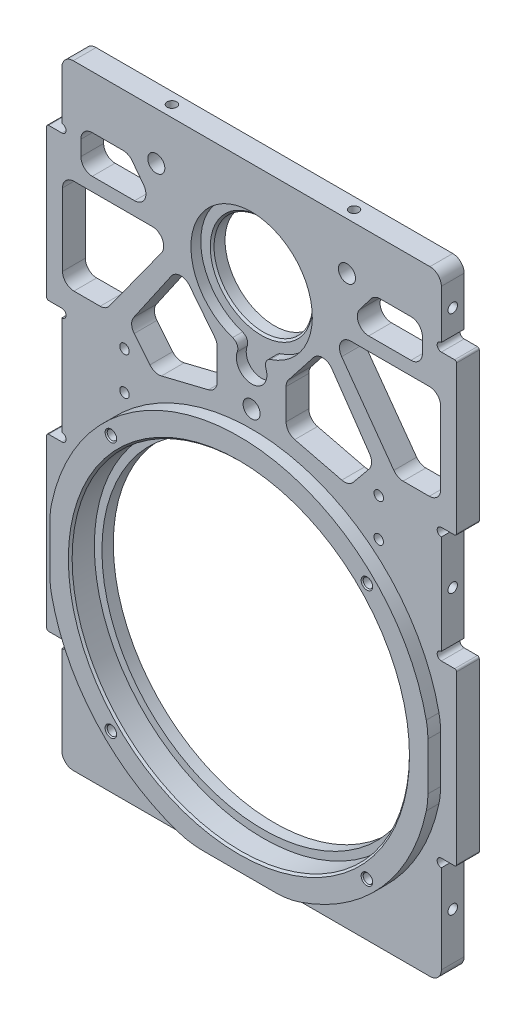
SolidWorks part; units mm, degrees
material "Thornel Mat VMA"
ref_plane "前视基准面" through (0, 0, 0) normal (0, 0, 1) x (1, 0, 0)
ref_plane "上视基准面" through (0, 0, 0) normal (0, 1, 0) x (1, 0, 0)
ref_plane "右视基准面" through (0, 0, 0) normal (1, 0, 0) x (0, 0, -1)
sketch "草图1" plane through (0, 0, 0) normal (0, 0, 1) x (1, 0, 0)
  line L1 (50, -123) -> (-50, -123)
  line L2 (50, -123) -> (50, 123)
  line L3 (50, 123) -> (-50, 123)
  line L4 (-50, -123) -> (-50, 123)
  line L5 (50, -123) -> (-50, 123) construction
  line L6 (50, 123) -> (-50, -123) construction
  circle A0 centre (0, 0) radius 44.45
  point P0 (0, 0)
  dimension "D2" = 88.9
  dimension "D3" = 123
  dimension "D1" = 100
extrude "凸台-拉伸1" add sketch "草图1" along normal blind 6
sketch "草图2" plane through (0, 0, 6) normal (0, 0, 1) x (1, 0, 0)
  line L0 (0, 0) -> (0, 84) construction
  circle A0 centre (0, 84) radius 13
  dimension "D1" = 26
  dimension "D2" = 84
extrude "切除-拉伸1" cut sketch "草图2" against normal blind 6
sketch "草图3" plane through (0, 0, 6) normal (0, 0, 1) x (1, 0, 0)
  line L0 (0, 84) -> (0, 55) construction
  circle A0 centre (0, 84) radius 29 construction
  circle A1 centre (0, 55) radius 2
  circle A2 centre (-25.1147, 98.5) radius 2
  circle A3 centre (25.1147, 98.5) radius 2
  point P11 (0, 84)
  dimension "D1" = 58
  dimension "D2" = 4
  dimension "D3" = 3
extrude "切除-拉伸2" cut sketch "草图3" against normal blind 10
sketch "草图4" plane through (0, 0, 6) normal (0, 0, 1) x (1, 0, 0)
  circle A0 centre (0, 84) radius 16
  dimension "D1" = 32
extrude "切除-拉伸3" cut sketch "草图4" against normal blind 2.6
sketch "草图5" plane through (0, 0, 6) normal (0, 0, 1) x (1, 0, 0)
  line L0 (0, 84) -> (0, 64.75) construction
  circle A0 centre (0, 64.75) radius 4.025
  dimension "D2" = 8.05
  dimension "D1" = 19.25
extrude "切除-拉伸4" cut sketch "草图5" against normal up to surface (2.6 mm away) up to face at (16, 84, 3.4)
fillet "圆角1" radius 2 2 edges at (2.1598, 68.1464, 4.7) (-2.1598, 68.1464, 4.7)
hole_wizard "打孔尺寸(%根据十字)槽沉头自攻螺钉的类型1" positions "3D草图6" profile "草图13" countersink size "ST4.2" standard "GB"
sketch3d "3D草图6"
  line L0 (25.1147, 98.5, 0) -> (25.1147, 98.5, 6) construction
  line L1 (-25.1147, 98.5, 0) -> (-25.1147, 98.5, 6) construction
  line L2 (0, 55, 0) -> (0, 55, 6) construction
  point P0 (25.1147, 98.5, 0)
  point P4 (-25.1147, 98.5, 0)
  point P8 (0, 55, 0)
sketch "草图13" plane through (25.1147, 98.5, 0) normal (1, 0, 0) x (0, 1, 0)
  line L0 (0, 0) -> (0, 9.8519)
  line L1 (0, 9.8519) -> (2.25, 8.5)
  line L2 (2.25, 8.5) -> (2.25, 2.45)
  line L3 (2.25, 2.45) -> (4.7, 0)
  line L5 (4.7, 0) -> (0, 0)
  line L6 (-2.25, 2.45) -> (-4.7, 0) construction
  line L10 (0, 9.8519) -> (-2.25, 8.5) construction
  line L11 (0, -6.35) -> (0, 107.95) construction
  dimension "孔直径" = 4.5
  dimension "孔深度" = 8.5
  dimension "近端锥形沉头孔直径" = 9.4
  dimension "近端锥形沉头孔角度" = 90
  dimension "导头角度" = 118
sketch "草图17" plane through (0, 0, 0) normal (0, 0, -1) x (-1, 0, 0)
  circle A0 centre (0, 0) radius 44.45 construction
  circle A1 centre (0, 0) radius 44.45
  circle A2 centre (0, 0) radius 42.45
  dimension "D1" = 2
extrude "凸台-拉伸3" add sketch "草图17" against normal blind 3
sketch "草图18" plane through (0, 0, 6) normal (0, 0, 1) x (1, 0, 0)
  circle A0 centre (0, 0) radius 44.45 construction
  circle A1 centre (0, 0) radius 44.45
  circle A2 centre (0, 0) radius 50.45
  dimension "D1" = 6
extrude "凸台-拉伸4" add sketch "草图18" along normal blind 3.35
sketch "草图20" plane through (0, 0, 9.35) normal (0, 0, 1) x (1, 0, 0)
  line L0 (0, 0) -> (47.7, 0) construction
  line L1 (0, 0) -> (33.729, 33.729) construction
  circle A0 centre (0, 0) radius 47.7 construction
  circle A1 centre (33.729, 33.729) radius 1.2
  circle A2 centre (33.729, -33.729) radius 1.2
  circle A3 centre (-33.729, -33.729) radius 1.2
  circle A4 centre (-33.729, 33.729) radius 1.2
  circle A5 centre (0, 0) radius 42.45 construction
  point P15 (0, 0)
  dimension "D1" = 5.25
  dimension "D3" = 2.4
  dimension "D2" = 45
  dimension "D4" = 4
extrude "切除-拉伸9" cut sketch "草图20" against normal blind 22.35
hole_wizard "M3 螺纹孔4" positions "3D草图8" profile "草图21" tap size "M3" standard "GB"
sketch3d "3D草图8"
  line L0 (33.729, 33.729, 0) -> (33.729, 33.729, 9.35) construction
  line L1 (33.729, -33.729, 0) -> (33.729, -33.729, 9.35) construction
  line L2 (-33.729, 33.729, 0) -> (-33.729, 33.729, 9.35) construction
  line L3 (-33.729, -33.729, 0) -> (-33.729, -33.729, 9.35) construction
  point P0 (33.729, 33.729, 9.35)
  point P4 (33.729, -33.729, 9.35)
  point P8 (-33.729, 33.729, 9.35)
  point P12 (-33.729, -33.729, 9.35)
sketch "草图21" plane through (33.729, 33.729, 9.35) normal (1, 0, 0) x (0, -1, 0)
  line L0 (0, 0) -> (0, 13.2511)
  line L1 (0, 13.2511) -> (1.25, 12.5)
  line L2 (1.25, 12.5) -> (1.25, 0.275)
  line L3 (1.25, 0.275) -> (1.525, 0)
  line L5 (1.525, 0) -> (0, 0)
  line L6 (-1.25, 0.275) -> (-1.525, 0) construction
  line L10 (0, 13.2511) -> (-1.25, 12.5) construction
  line L11 (0, -6.35) -> (0, 107.95) construction
  dimension "螺纹孔钻头直径" = 2.5
  dimension "螺纹孔钻头深度" = 12.5
  dimension "近端锥形沉头孔直径" = 3.05
  dimension "近端锥形沉头孔角度" = 90
  dimension "导头角度" = 118
cosmetic thread "孔螺蚊线15" parameters "D1"=9.35, "D2"=3
cosmetic thread "孔螺蚊线16" parameters "D1"=9.35, "D2"=3
cosmetic thread "孔螺蚊线17" parameters "D1"=9.35, "D2"=3
cosmetic thread "孔螺蚊线18" parameters "D1"=9.35, "D2"=3
chamfer "倒角1" distance 0.5 angle 45 1 edges at (44.45, 0, 9.35)
sketch "草图22" plane through (0, 0, 6) normal (0, 0, 1) x (1, 0, 0)
  line L0 (-50, -6.7233) -> (-50, -123) construction
  line L1 (50, -123) -> (-50, -123)
  line L2 (50, -123) -> (50, -51)
  line L3 (50, -51) -> (-50, -51)
  line L4 (-50, -123) -> (-50, -51)
  dimension "D1" = 72
sketch "草图23" plane through (0, 0, 6) normal (0, 0, 1) x (1, 0, 0)
  line L0 (-50, 123) -> (-50, 6.7233) construction
  line L1 (50, 123) -> (-50, 123)
  line L2 (50, 123) -> (50, 111)
  line L3 (50, 111) -> (-50, 111)
  line L4 (-50, 123) -> (-50, 111)
  dimension "D1" = 12
extrude "切除-拉伸11" cut sketch "草图23" against normal blind 10
sketch "草图24" plane through (0, 0, 6) normal (0, 0, 1) x (1, 0, 0)
  line L0 (-50, 0) -> (50, 0) construction
  line L1 (0, 0) -> (0, 122.891) construction
  line L2 (50, 6.7233) -> (50, -6.7233) construction
  line L3 (-54, 22.5) -> (-46, -22.5) construction
  line L4 (54, -22.5) -> (46, -22.5)
  line L5 (54, -22.5) -> (54, 22.5)
  line L6 (54, 22.5) -> (46, 22.5)
  line L7 (46, -22.5) -> (46, 22.5)
  line L8 (54, -22.5) -> (46, 22.5) construction
  line L9 (54, 22.5) -> (46, -22.5) construction
  line L10 (-54, -22.5) -> (-46, 22.5) construction
  line L11 (-50, 6.7233) -> (-50, -6.7233) construction
  line L12 (-46, -22.5) -> (-46, 22.5)
  line L13 (-54, 22.5) -> (-46, 22.5)
  line L14 (-54, -22.5) -> (-54, 22.5)
  line L15 (-54, -22.5) -> (-46, -22.5)
  line L16 (50, 6.7233) -> (50, 111) construction
  dimension "D1" = 45
  dimension "D2" = 4
extrude "凸台-拉伸5" add sketch "草图24" against normal up to surface (6 mm away) up to face at (34.979, 33.729, 0)
sketch "草图25" plane through (0, 0, 9.35) normal (0, 0, 1) x (1, 0, 0)
  line L0 (50, -22.5) -> (50, 22.5)
  line L1 (0, 0) -> (0, -64.4708) construction
  line L2 (50, -22.5) -> (54, -22.5)
  line L3 (54, -22.5) -> (54, 22.5)
  line L4 (54, 22.5) -> (50, 22.5)
  line L5 (49.8, -22.7) -> (49.8, 22.7)
  line L6 (54.2, 22.7) -> (49.8, 22.7)
  line L7 (54.2, -22.7) -> (54.2, 22.7)
  line L8 (49.8, -22.7) -> (54.2, -22.7)
  line L9 (-49.8, -22.7) -> (-54.2, -22.7)
  line L10 (-54.2, -22.7) -> (-54.2, 22.7)
  line L11 (-54.2, 22.7) -> (-49.8, 22.7)
  line L12 (-49.8, -22.7) -> (-49.8, 22.7)
  line L13 (-54, 22.5) -> (-50, 22.5)
  line L14 (-54, -22.5) -> (-54, 22.5)
  line L15 (-50, -22.5) -> (-54, -22.5)
  line L16 (-50, -22.5) -> (-50, 22.5)
  circle M11 centre (0, 0) radius 50.45
  dimension "D1" = 0.2
extrude "切除-拉伸12" cut sketch "草图25" against normal up to surface (3.35 mm away) contours L3 L4 L0 L2 M11 | L5 L8 L7 L6 L0 L4 L3 L2 M11 | L5 L0 M11 | L0 M11 | L15 L16 L13 L14 M11 | L16 L15 L14 L13 L12 L11 L10 L9 M11 | L16 L12 M11 | L16 M11 region at (52, -22.5456, 9.35) region at (52.0418, 0, 9.35) region at (49.897, 0, 9.35) region at (50.1801, 0, 9.35) region at (-49.897, 0, 9.35) region at (-49.8456, -15.3862, 9.35) region at (-50.1801, 0, 9.35) region at (-52.0418, 0, 9.35) up to face at (50.45, 0, 6)
fillet "圆角2" radius 20 4 edges at (-49.8, 8.0723, 7.675) (49.8, 8.0723, 7.675) (49.8, -8.0723, 7.675) (-49.8, -8.0723, 7.675)
sketch "草图26" plane through (0, 0, 6) normal (0, 0, 1) x (1, 0, 0)
  line L0 (50, -123) -> (50, -22.5) construction
  line L1 (50, 22.5) -> (50, 111) construction
  line L2 (-50, -22.5) -> (-50, -123) construction
  line L3 (-50, 111) -> (-50, 22.5) construction
  circle A0 centre (50, -23.6) radius 1.1
  circle A1 centre (50, 23.6) radius 1.1
  circle A2 centre (-50, -23.6) radius 1.1
  circle A3 centre (-50, 23.6) radius 1.1
  dimension "D1" = 2.2
extrude "切除-拉伸13" cut sketch "草图26" against normal blind 10
fillet "圆角3" radius 0.5 4 edges at (-54, -22.5, 3) (-54, 22.5, 3) (54, 22.5, 3) (54, -22.5, 3)
sketch "草图27" plane through (0, 0, 6) normal (0, 0, 1) x (1, 0, 0)
  line L0 (50, 24.7) -> (50, 111) construction
  line L1 (46, 53) -> (54, 53)
  line L2 (46, 53) -> (46, 93)
  line L3 (46, 93) -> (54, 93)
  line L4 (54, 53) -> (54, 93)
  line L5 (46, 53) -> (54, 93) construction
  line L6 (46, 93) -> (54, 53) construction
  line L7 (54, -22) -> (54, 22) construction
  line L8 (0, 0) -> (0, 27.5461) construction
  line L9 (-46, 93) -> (-54, 53) construction
  line L10 (-46, 53) -> (-54, 93) construction
  line L11 (-54, 53) -> (-54, 93)
  line L12 (-46, 93) -> (-54, 93)
  line L13 (-46, 53) -> (-46, 93)
  line L14 (-46, 53) -> (-54, 53)
  line L15 (-50, 111) -> (50, 111) construction
  point P0 (50, 73)
  point P16 (-50, 73)
  dimension "D1" = 18
  dimension "D2" = 40
extrude "凸台-拉伸6" add sketch "草图27" against normal up to surface (6 mm away) up to face at (0, -1.2, 0)
sketch "草图28" plane through (0, 0, 6) normal (0, 0, 1) x (1, 0, 0)
  line L0 (50, 24.7) -> (50, 53) construction
  line L1 (-50, 53) -> (-50, 24.7) construction
  line L2 (50, 93) -> (50, 111) construction
  line L3 (-50, 111) -> (-50, 93) construction
  circle A0 centre (50, 51.9) radius 1.1
  circle A1 centre (-50, 51.9) radius 1.1
  circle A2 centre (50, 94.1) radius 1.1
  circle A3 centre (-50, 94.1) radius 1.1
  dimension "D1" = 2.2
extrude "切除-拉伸14" cut sketch "草图28" against normal blind 10
fillet "圆角5" radius 0.5 4 edges at (-54, 93, 3) (-54, 53, 3) (54, 53, 3) (54, 93, 3)
extrude "切除-拉伸15" cut sketch "草图22" against normal blind 10
fillet "圆角6" radius 3 4 edges at (50, 111, 3) (-50, 111, 3) (-50, -51, 3) (50, -51, 3)
sketch "草图30" plane through (50, 0, 0) normal (1, 0, 0) x (0, 0, -1)
  line L0 (-6, 37.75) -> (0, 37.75) construction
  line L1 (-6, 24.7) -> (-6, 50.8) construction
  line L2 (0, 24.7) -> (0, 50.8) construction
  line L3 (-6, 101.6) -> (0, 101.6) construction
  line L4 (-6, 95.2) -> (-6, 108) construction
  line L5 (0, 95.2) -> (0, 108) construction
  line L6 (-6, -36.35) -> (0, -34.979) construction
  line L7 (-6, -48) -> (-6, -24.7) construction
  circle A0 centre (-3, -35.6645) radius 1.25
  circle A1 centre (-3, 37.75) radius 1.25
  circle A2 centre (-3, 101.6) radius 1.25
  dimension "D1" = 2.5
extrude "切除-拉伸17" cut sketch "草图30" against normal blind 8
cosmetic thread "孔螺蚊线20" parameters "D1"=8, "D2"=3
cosmetic thread "孔螺蚊线21" parameters "D1"=8, "D2"=3
cosmetic thread "孔螺蚊线22" parameters "D1"=8, "D2"=3
hole_wizard "M3 螺纹孔6" positions "3D草图10" profile "草图32" tap size "M3" standard "GB"
sketch3d "3D草图10"
  line L0 (42, -35.6645, 3) -> (50, -35.6645, 3) construction
  line L1 (42, 37.75, 3) -> (50, 37.75, 3) construction
  line L2 (42, 101.6, 3) -> (50, 101.6, 3) construction
  point P0 (50, -35.6645, 3)
  point P4 (50, 37.75, 3)
  point P8 (50, 101.6, 3)
sketch "草图32" plane through (50, -35.6645, 3) normal (0, 1, 0) x (0, 0, -1)
  line L0 (0, 0) -> (0, 11.2511)
  line L1 (0, 11.2511) -> (1.25, 10.5)
  line L2 (1.25, 10.5) -> (1.25, 0)
  line L5 (1.25, 0) -> (0, 0)
  line L10 (0, 11.2511) -> (-1.25, 10.5) construction
  line L11 (0, -6.35) -> (0, 107.95) construction
  dimension "螺纹孔钻头直径" = 2.5
  dimension "螺纹孔钻头深度" = 10.5
  dimension "导头角度" = 118
cosmetic thread "孔螺蚊线36" parameters "D1"=8, "D2"=3.5
cosmetic thread "孔螺蚊线37" parameters "D1"=8, "D2"=3.5
cosmetic thread "孔螺蚊线38" parameters "D1"=8, "D2"=3.5
mirror "镜向2" about plane through (0, 0, 0) normal (1, 0, 0) of "M3 螺纹孔6", "切除-拉伸17"
cosmetic thread "孔螺蚊线39" parameters "D1"=8, "D2"=3.5
cosmetic thread "孔螺蚊线40" parameters "D1"=8, "D2"=3.5
cosmetic thread "孔螺蚊线41" parameters "D1"=8, "D2"=3.5
cosmetic thread "孔螺蚊线52" parameters "D1"=8, "D2"=3.5
cosmetic thread "孔螺蚊线53" parameters "D1"=8, "D2"=3.5
cosmetic thread "孔螺蚊线54" parameters "D1"=8, "D2"=3
sketch "草图33" plane through (0, 0, 0) normal (0, 0, -1) x (-1, 0, 0)
  line L0 (0, 0) -> (0, 84) construction
  line L1 (0, 42) -> (-33.5, 42) construction
  line L2 (-33.5, 42) -> (-33.5, 52) construction
  circle A0 centre (-33.5, 42) radius 1.25
  circle A1 centre (33.5, 42) radius 1.25
  circle A2 centre (-33.5, 52) radius 1.25
  circle A3 centre (33.5, 52) radius 1.25
  dimension "D1" = 2.5
  dimension "D2" = 67
  dimension "D3" = 10
extrude "切除-拉伸18" cut sketch "草图33" against normal blind 10
cosmetic thread "孔螺蚊线26" parameters "D1"=6, "D2"=3
cosmetic thread "孔螺蚊线27" parameters "D1"=6, "D2"=3
cosmetic thread "孔螺蚊线28" parameters "D1"=6, "D2"=3
cosmetic thread "孔螺蚊线29" parameters "D1"=6, "D2"=3
hole_wizard "M3 螺纹孔7" positions "3D草图11" profile "草图34" tap size "M3" standard "GB"
sketch3d "3D草图11"
  line L0 (33.5, 42, 6) -> (33.5, 42, 0) construction
  line L1 (33.5, 52, 6) -> (33.5, 52, 0) construction
  line L2 (-33.5, 42, 6) -> (-33.5, 42, 0) construction
  line L3 (-33.5, 52, 6) -> (-33.5, 52, 0) construction
  point P0 (33.5, 42, 0)
  point P4 (33.5, 52, 0)
  point P8 (-33.5, 42, 0)
  point P12 (-33.5, 52, 0)
sketch "草图34" plane through (33.5, 42, 0) normal (1, 0, 0) x (0, 1, 0)
  line L0 (0, 0) -> (0, 13.2511)
  line L1 (0, 13.2511) -> (1.25, 12.5)
  line L2 (1.25, 12.5) -> (1.25, 0)
  line L5 (1.25, 0) -> (0, 0)
  line L10 (0, 13.2511) -> (-1.25, 12.5) construction
  line L11 (0, -6.35) -> (0, 107.95) construction
  dimension "螺纹孔钻头直径" = 2.5
  dimension "螺纹孔钻头深度" = 12.5
  dimension "导头角度" = 118
cosmetic thread "孔螺蚊线42" parameters "D1"=10, "D2"=3.5
cosmetic thread "孔螺蚊线43" parameters "D1"=10, "D2"=3.5
cosmetic thread "孔螺蚊线44" parameters "D1"=10, "D2"=3.5
cosmetic thread "孔螺蚊线45" parameters "D1"=10, "D2"=3.5
chamfer "倒角2" distance 0.5 angle 45 1 edges at (13, 84, 3.4)
sketch "草图35" plane through (0, -51, 0) normal (0, -1, 0) x (1, 0, 0)
  line L0 (0, 0) -> (0, 6) construction
  line L1 (47, 0) -> (-47, 0) construction
  line L2 (47, 6) -> (-47, 6) construction
  line L3 (24, 3) -> (-24, 3) construction
  circle A0 centre (-24, 3) radius 1.25
  circle A1 centre (24, 3) radius 1.25
  point P10 (0, 3)
  dimension "D1" = 2.5
  dimension "D2" = 48
extrude "切除-拉伸19" cut sketch "草图35" against normal blind 6
cosmetic thread "孔螺蚊线30" parameters "D1"=6, "D2"=3
cosmetic thread "孔螺蚊线31" parameters "D1"=6, "D2"=3
cosmetic thread "孔螺蚊线34" parameters "D1"=6, "D2"=3
cosmetic thread "孔螺蚊线35" parameters "D1"=6, "D2"=3
hole_wizard "M3 螺纹孔8" positions "3D草图12" profile "草图36" tap size "M3" standard "GB"
sketch3d "3D草图12"
  line L0 (-24, -45, 3) -> (-24, -51, 3) construction
  line L1 (24, -45, 3) -> (24, -51, 3) construction
  point P0 (-24, -51, 3)
  point P4 (24, -51, 3)
sketch "草图36" plane through (-24, -51, 3) normal (1, 0, 0) x (0, 0, -1)
  line L0 (0, 0) -> (0, 6.7511)
  line L1 (0, 6.7511) -> (1.25, 6)
  line L2 (1.25, 6) -> (1.25, 0)
  line L5 (1.25, 0) -> (0, 0)
  line L10 (0, 6.7511) -> (-1.25, 6) construction
  line L11 (0, -6.35) -> (0, 107.95) construction
  dimension "螺纹孔钻头直径" = 2.5
  dimension "螺纹孔钻头深度" = 6
  dimension "导头角度" = 118
cosmetic thread "孔螺蚊线46" parameters "D1"=6, "D2"=3.5
cosmetic thread "孔螺蚊线47" parameters "D1"=6, "D2"=3.5
ref_plane "基准面1" through (0, 30, 0) normal (0, -1, 0) x (-1, 0, 0)
mirror "镜向3" about plane through (0, 30, 0) normal (0, -1, 0) of "M3 螺纹孔8", "切除-拉伸19"
cosmetic thread "孔螺蚊线32" parameters "D1"=6, "D2"=3
cosmetic thread "孔螺蚊线33" parameters "D1"=6, "D2"=3
cosmetic thread "孔螺蚊线48" parameters "D1"=6, "D2"=3.5
cosmetic thread "孔螺蚊线49" parameters "D1"=6, "D2"=3
cosmetic thread "孔螺蚊线50" parameters "D1"=6, "D2"=3
cosmetic thread "孔螺蚊线51" parameters "D1"=6, "D2"=3.5
sketch "草图38" plane through (0, 0, 9.35) normal (0, 0, 1) x (1, 0, 0)
  line L1 (12.5, -52.0231) -> (-12.5, -52.0231)
  line L2 (12.5, -52.0231) -> (12.5, -48.8769)
  line L3 (12.5, -48.8769) -> (-12.5, -48.8769)
  line L4 (-12.5, -52.0231) -> (-12.5, -48.8769)
  line L5 (12.5, -52.0231) -> (-12.5, -48.8769) construction
  line L6 (12.5, -48.8769) -> (-12.5, -52.0231) construction
  arc A0 (-49.3731, -10.3683) -> (49.3731, -10.3683) centre (0, 0) ccw construction
  point P0 (0, -50.45)
  dimension "D1" = 25
extrude "切除-拉伸20" cut sketch "草图38" against normal up to surface (3.35 mm away) up to face at (-32.25, 42, 6)
fillet "圆角7" radius 20 2 edges at (-12.5, -48.8769, 7.675) (12.5, -48.8769, 7.675)
sketch "草图39" plane through (0, 0, 6) normal (0, 0, 1) x (1, 0, 0)
  line L0 (49.8268, 83.5676) -> (20.2964, 83.5676)
  line L1 (20.2964, 83.5676) -> (38.3812, 58.5059)
  line L2 (38.3812, 58.5059) -> (49.8268, 58.5059)
  line L3 (49.8268, 58.5059) -> (49.8268, 83.5676)
  line L4 (44.992, 87.1196) -> (24.8185, 87.1196)
  line L5 (24.8185, 87.1196) -> (32.3625, 97.0851)
  line L6 (32.3625, 97.0851) -> (44.992, 97.0851)
  line L7 (44.992, 97.0851) -> (44.992, 87.1196)
  line L8 (32.3625, 58.5059) -> (18.845, 78.1408)
  line L9 (18.845, 78.1408) -> (9.0768, 65.7087)
  line L10 (9.0768, 65.7087) -> (9.0768, 54.2632)
  line L11 (9.0768, 54.2632) -> (25.6037, 50.2178)
  line L12 (25.6037, 50.2178) -> (32.3625, 58.5059)
  line L13 (0, 0) -> (0, 131.7682) construction
  line L14 (-25.6037, 50.2178) -> (-32.3625, 58.5059)
  line L15 (-9.0768, 54.2632) -> (-25.6037, 50.2178)
  line L16 (-9.0768, 65.7087) -> (-9.0768, 54.2632)
  line L17 (-18.845, 78.1408) -> (-9.0768, 65.7087)
  line L18 (-32.3625, 58.5059) -> (-18.845, 78.1408)
  line L19 (-44.992, 97.0851) -> (-44.992, 87.1196)
  line L20 (-32.3625, 97.0851) -> (-44.992, 97.0851)
  line L21 (-24.8185, 87.1196) -> (-32.3625, 97.0851)
  line L22 (-44.992, 87.1196) -> (-24.8185, 87.1196)
  line L23 (-49.8268, 58.5059) -> (-49.8268, 83.5676)
  line L24 (-38.3812, 58.5059) -> (-49.8268, 58.5059)
  line L25 (-20.2964, 83.5676) -> (-38.3812, 58.5059)
  line L26 (-49.8268, 83.5676) -> (-20.2964, 83.5676)
extrude "切除-拉伸21" cut sketch "草图39" against normal blind 10
fillet "圆角8" radius 3 26 edges at (38.3812, 58.5059, 3) (20.2964, 83.5676, 3) (49.8268, 83.5676, 3) (-49.8268, 83.5676, 3) (-20.2964, 83.5676, 3) (-38.3812, 58.5059, 3) (-49.8268, 58.5059, 3) (-24.8185, 87.1196, 3) (-44.992, 87.1196, 3) (-44.992, 97.0851, 3) (-32.3625, 97.0851, 3) (-32.3625, 58.5059, 3) (-18.845, 78.1408, 3) (-9.0768, 65.7087, 3) (-9.0768, 54.2632, 3) (-25.6037, 50.2178, 3) (18.845, 78.1408, 3) (32.3625, 58.5059, 3) (25.6037, 50.2178, 3) (9.0768, 54.2632, 3) (9.0768, 65.7087, 3) (24.8185, 87.1196, 3) (32.3625, 97.0851, 3) (44.992, 97.0851, 3) (44.992, 87.1196, 3) (49.8268, 58.5059, 3)
